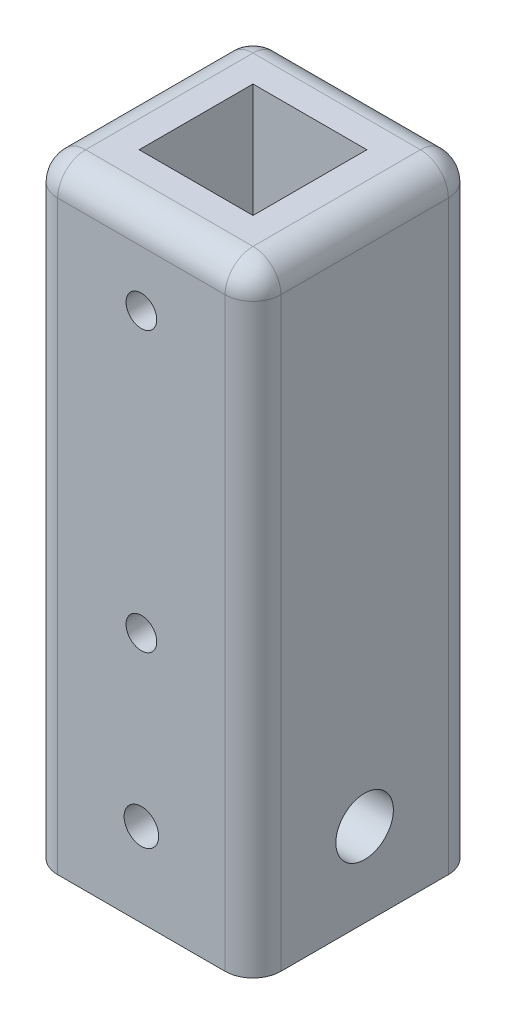
SolidWorks part; units mm, degrees
ref_plane "Front Plane" through (0, 0, 0) normal (0, 0, 1) x (1, 0, 0)
ref_plane "Top Plane" through (0, 0, 0) normal (0, 1, 0) x (1, 0, 0)
ref_plane "Right Plane" through (0, 0, 0) normal (1, 0, 0) x (0, 0, -1)
sketch "Sketch1" plane through (0, 0, 0) normal (0, 1, 0) x (1, 0, 0)
  line L1 (0, 0) -> (20.4, 0)
  line L2 (0, 0) -> (0, 20.4)
  line L3 (0, 20.4) -> (20.4, 20.4)
  line L4 (20.4, 0) -> (20.4, 20.4)
  line L5 (-9.8, -9.8) -> (30.2, -9.8)
  line L6 (-9.8, -9.8) -> (-9.8, 30.2)
  line L7 (-9.8, 30.2) -> (30.2, 30.2)
  line L8 (30.2, -9.8) -> (30.2, 30.2)
  dimension "D1" = 40
  dimension "D2" = 40
  dimension "D3" = 20.4
  dimension "D4" = 20.4
  dimension "D5" = 9.8
  dimension "D6" = 9.8
extrude "Boss-Extrude1" add sketch "Sketch1" along normal blind 80
extrude "Boss-Extrude2" add sketch "Sketch1<2>" against normal blind 30 contours L1 L4 L3 L2 | L5 L8 L7 L6 L4 L1 L2 L3 region at (10.2, 0, -10.2) region at (-9.2343, 0, -10.2)
sketch "Sketch1<2>" plane through (0, 0, 0) normal (0, 1, 0) x (1, 0, 0) same geometry as "Sketch1"
sketch "Sketch2" plane through (0, 0, 0) normal (0, 0, -1) x (-1, 0, 0)
  line L0 (-30.2, 80) -> (9.8, 80) construction
  line L1 (-30.2, 15) -> (9.8, 15) construction
  line L2 (-30.2, 80) -> (-30.2, -30) construction
  line L3 (9.8, 80) -> (9.8, -30) construction
  circle A0 centre (-10.2, 15) radius 2.75
  circle A1 centre (-10.2, 65) radius 2.75
  point P14 (-10.2, 15)
  dimension "D1" = 5.5
  dimension "D2" = 5.5
  dimension "D3" = 15
  dimension "D4" = 15
extrude "Cut-Extrude1" cut sketch "Sketch2" against normal through all both and the other way through all
sketch "Sketch3" plane through (-9.8, 0, 0) normal (-1, 0, 0) x (0, 0, 1)
  line L0 (9.8, 80) -> (9.8, -30) construction
  line L1 (-30.2, -30) -> (9.8, -30)
  line L2 (-30.2, -30) -> (-30.2, 0)
  line L3 (-30.2, 0) -> (9.8, 0)
  line L4 (9.8, -30) -> (9.8, 0)
  circle A0 centre (-10.2, -15) radius 7
  circle A1 centre (-10.2, -15) radius 5.15
  point P11 (-10.2, -30)
  point P12 (-30.2, -15)
  dimension "D2" = 14
  dimension "D3" = 10.3
  dimension "D1" = 30
extrude "Cut-Extrude4" cut sketch "Sketch3" against normal through all contours A1 region at (-9.8, -15, -10.2)
fillet "Fillet1" radius 5 4 edges at (-9.8, 25, -30.2) (-9.8, 25, 9.8) (30.2, 25, 9.8) (30.2, 25, -30.2)
sketch "Sketch4" plane through (0, 0, 9.8) normal (0, 0, 1) x (1, 0, 0)
  line L0 (-4.8, -30) -> (25.2, -30) construction
  line L1 (25.2, -15) -> (-4.8, -15) construction
  line L2 (25.2, -30) -> (25.2, 80) construction
  line L3 (-4.8, 80) -> (-4.8, -30) construction
  circle A0 centre (10.2, -15) radius 3.1
  circle A1 centre (10.2, -15) radius 2.75
  point P11 (10.2, -15)
  dimension "D1" = 6.2
  dimension "D3" = 5.5
  dimension "D2" = 15
extrude "Cut-Extrude6" cut sketch "Sketch4" against normal blind 10.5 contours L1 A1 | A1 L1 | A0 L1 A1 | L1 A0 A1 region at (10.2, -18.0307, 9.8) region at (13.125, -14.9307, 9.8) region at (10.2, -16.1671, 9.8) region at (10.2, -13.8329, 9.8)
extrude "Cut-Extrude7" cut sketch "Sketch4<3>" against normal blind 20 contours A1 L1 | L1 A1 region at (10.2, -16.1671, 9.8) region at (10.2, -13.8329, 9.8)
sketch "Sketch4<3>" plane through (0, 0, 9.8) normal (0, 0, 1) x (1, 0, 0) same geometry as "Sketch4"
fillet "Fillet2" radius 5 8 edges at (-8.3355, 80, -28.7355) (10.2, 80, -30.2) (28.7355, 80, -28.7355) (30.2, 80, -10.2) (28.7355, 80, 8.3355) (10.2, 80, 9.8) (-8.3355, 80, 8.3355) (-9.8, 80, -10.2)
